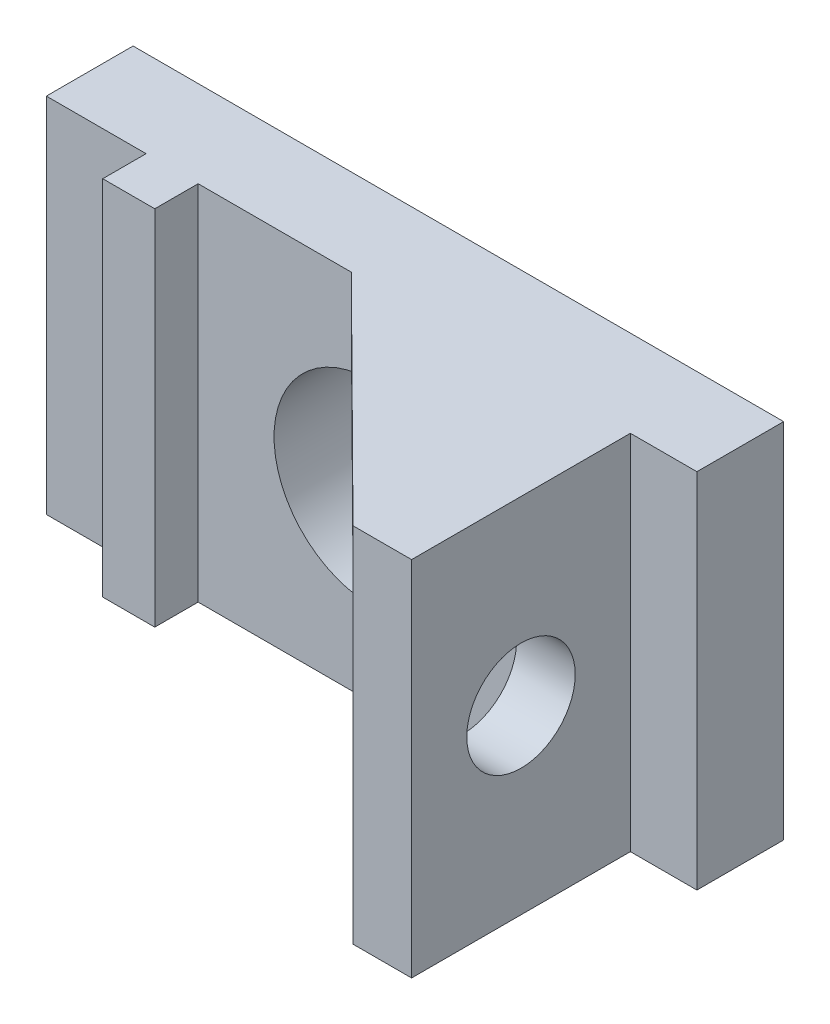
SolidWorks part; units mm, degrees
ref_plane "Спереди" through (0, 0, 0) normal (0, 0, 1) x (1, 0, 0)
ref_plane "Сверху" through (0, 0, 0) normal (0, 1, 0) x (1, 0, 0)
ref_plane "Справа" through (0, 0, 0) normal (1, 0, 0) x (0, 0, -1)
sketch "Эскиз2" plane through (0, 0, 0) normal (0, 0, 1) x (1, 0, 0)
  line L0 (23, -83.5469) -> (23, 0)
  line L1 (0, 0) -> (150, 0)
  line L2 (0, 0) -> (0, -83.5469)
  line L3 (0, -83.5469) -> (150, -83.5469)
  line L4 (150, 0) -> (150, -83.5469)
  line L5 (35, 0) -> (35, -83.5469)
  line L6 (0, -41.7735) -> (150, -41.7735) construction
  line L7 (75, -83.5469) -> (75, 0) construction
  circle A0 centre (75, -41.7735) radius 22.5
  point P15 (0, 0)
  point P16 (0, 0)
  dimension "D4" = 45
  dimension "D1" = 83.5469
  dimension "D2" = 150
  dimension "D3" = 12
  dimension "D5" = 23
extrude "Бобышка-Вытянуть1" add sketch "Эскиз2" along normal blind 20 contours L2 L3 L0 L1 | L1 L5 L3 L4 A0 region at (11.5, -41.7735, 0) region at (36.4214, -41.7735, 0)
extrude "Бобышка-Вытянуть2" add sketch "Эскиз2<3>" along normal blind 30 contours L5 L1 L0 L3 region at (29, -41.7735, 0)
sketch "Эскиз2<3>" plane through (0, 0, 0) normal (0, 0, 1) x (1, 0, 0) same geometry as "Эскиз2"
sketch "Эскиз4" plane through (0, 0, 0) normal (0, 1, 0) x (1, 0, 0)
  line L0 (134.6631, -20) -> (134.6631, -70.4495)
  line L1 (35, -20) -> (150, -20) construction
  line L2 (134.6631, -70.4495) -> (121.1585, -70.4495)
  line L3 (121.1585, -70.4495) -> (121.1585, -20)
  line L4 (121.1585, -20) -> (134.6631, -20)
  line L5 (35, -20) -> (150, -20) construction
  point P4 (0, 0)
  point P7 (134.1124, -20)
  point P10 (121.1585, -20)
  point P11 (134.6631, -70.4495)
extrude "Бобышка-Вытянуть4" add sketch "Эскиз4" against normal up to surface (83.5469 mm away) up to face at (52, -83.5469, 17.5)
sketch "Эскиз6" plane through (121.1585, 0, 0) normal (-1, 0, 0) x (0, 0, 1)
  line L0 (70.4495, -41.7735) -> (20, -41.7735) construction
  line L1 (70.4495, -83.5469) -> (70.4495, 0) construction
  line L2 (45.2248, 0) -> (45.2248, -83.5469) construction
  line L3 (20, 0) -> (70.4495, 0) construction
  line L4 (70.4495, -83.5469) -> (20, -83.5469) construction
  line L5 (20, -83.5469) -> (20, 0) construction
  circle A0 centre (45.2248, -41.7735) radius 12.5
  point P12 (0, 0)
  point P14 (21.2104, -41.7735)
  point P15 (20, -41.7735)
  dimension "D1" = 25
extrude "Вырез-Вытянуть1" cut sketch "Эскиз6" against normal through all
sketch "Эскиз7" plane through (0, 0, 0) normal (0, 1, 0) x (1, 0, 0)
  line L0 (121.1585, -70.4495) -> (70.3209, -20)
  line L1 (35, -20) -> (121.1585, -20) construction
  line L2 (70.3209, -20) -> (121.1585, -20)
  line L3 (121.1585, -20) -> (121.1585, -70.4495)
  point P5 (74.8109, -20)
  point P8 (70.3209, -20)
extrude "Бобышка-Вытянуть5" add sketch "Эскиз7" against normal blind 10
